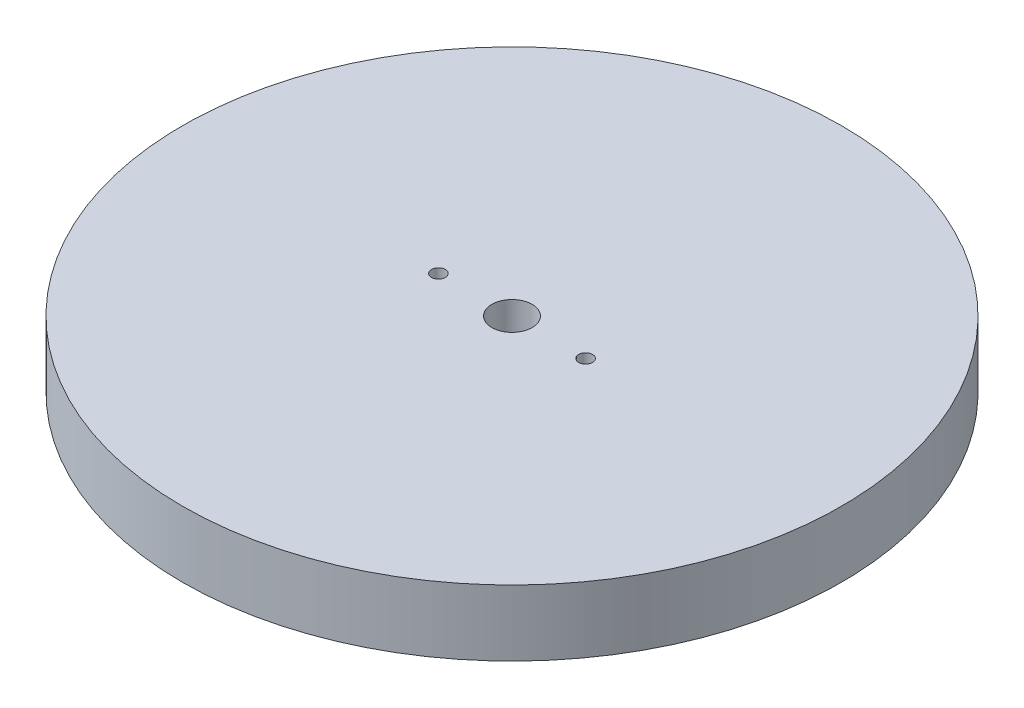
SolidWorks part; units mm, degrees
ref_plane "Front Plane" through (0, 0, 0) normal (0, 0, 1) x (1, 0, 0)
ref_plane "Top Plane" through (0, 0, 0) normal (0, 1, 0) x (1, 0, 0)
ref_plane "Right Plane" through (0, 0, 0) normal (1, 0, 0) x (0, 0, -1)
sketch "Sketch1" plane through (0, 0, 0) normal (0, 1, 0) x (1, 0, 0)
  circle A2 centre (-29.4335, -19.1453) radius 45
  circle A3 centre (-29.4335, -19.1453) radius 2.75
  circle A4 centre (-39.4835, -19.1453) radius 0.95
  circle A5 centre (-19.3835, -19.1453) radius 0.95
  dimension "D2" = 1.9
  dimension "D3" = 90
  dimension "D1" = 5.5
  dimension "D6" = 1.9
  dimension "D4" = 10.05
  dimension "D5" = 10.05
extrude "Boss-Extrude1" add sketch "Sketch1" along normal blind 9
